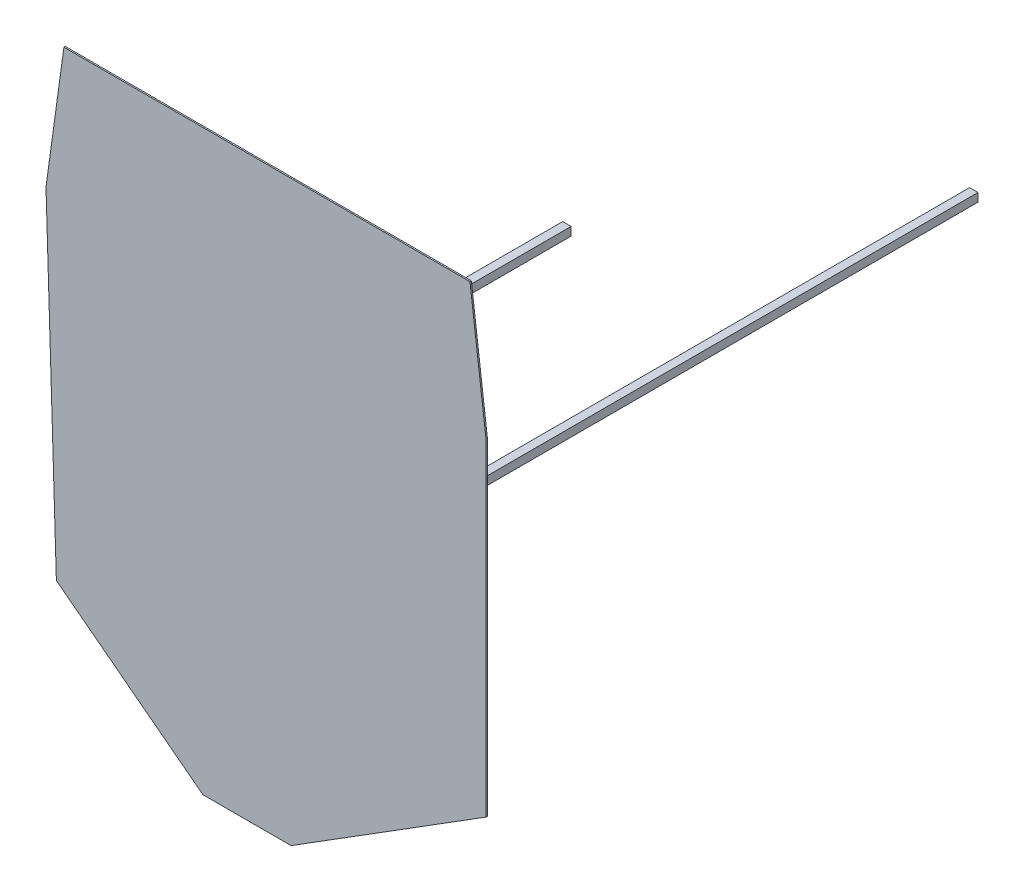
SolidWorks part; units mm, degrees
ref_plane "Front" through (0, 0, 0) normal (0, 0, 1) x (1, 0, 0)
ref_plane "Top" through (0, 0, 0) normal (0, 1, 0) x (1, 0, 0)
ref_plane "Right" through (0, 0, 0) normal (1, 0, 0) x (0, 0, -1)
sketch "Esquisse1" plane through (0, 0, 0) normal (0, 0, 1) x (1, 0, 0)
  line L1 (0, 0) -> (50, 0)
  line L2 (0, 0) -> (0, 50)
  line L3 (0, 50) -> (50, 50)
  line L4 (50, 0) -> (50, 50)
  dimension "D1" = 50
  dimension "D2" = 50
extrude "Boss.-Extru.1" add sketch "Esquisse1" along normal blind 5
sketch "Esquisse2" plane through (0, 0, 5) normal (0, 0, 1) x (1, 0, 0)
  line L0 (-5.6535, 9.3332) -> (57.2852, 53.4636)
  line L1 (57.2852, 53.4636) -> (231.6916, 53.4636)
  line L2 (231.6916, 53.4636) -> (285.9358, -3.0527)
  line L3 (285.9358, -3.0527) -> (284, -82.5096)
  line L4 (284, -82.5096) -> (207.7062, -129.7611)
  line L5 (207.7062, -129.7611) -> (50.4315, -129.7611)
  line L6 (50.4315, -129.7611) -> (-5.6535, -85.3866)
  line L7 (-5.6535, -85.3866) -> (-5.6535, 9.3332)
  line L8 (261, -129.7611) -> (23, -129.7611) construction
  line L9 (284, 24.7389) -> (284, -104.2611) construction
extrude "Boss.-Extru.2" add sketch "Esquisse2" against normal up to vertex (5 mm away) up to point (0, 50, 0)
sketch "Esquisse3" plane through (0, 0, 0) normal (0, 0, -1) x (-1, 0, 0)
  line L0 (0, -121.7217) -> (6, -121.7217)
  line L1 (6, -121.7217) -> (6, -115.7217)
  line L2 (6, -115.7217) -> (0, -115.7217)
  line L4 (0, -115.7217) -> (0, -121.7217)
  line L6 (-284, 44.2389) -> (-290, 44.2389)
  line L7 (-284, 44.2389) -> (-284, 50.2389)
  line L8 (-284, 50.2389) -> (-290, 50.2389)
  line L9 (-290, 44.2389) -> (-290, 50.2389)
  dimension "D1" = 6
  dimension "D2" = 6
  dimension "D3" = 6
  dimension "D4" = 6
extrude "Boss.-Extru.3" add sketch "Esquisse3" along normal blind 350
sketch "Esquisse4" plane through (0, 0, 5) normal (0, 0, 1) x (1, 0, 0)
  line L0 (-5.5339, 170.1435) -> (283.89, 170.1435)
  line L1 (283.89, 170.1435) -> (295.4804, 77.4204)
  line L2 (295.4804, 77.4204) -> (295.4804, -154.5668)
  line L3 (295.4804, -154.5668) -> (156.3957, -241.7353)
  line L4 (156.3957, -241.7353) -> (93.5299, -241.7353)
  line L5 (93.5299, -241.7353) -> (-10.9091, -161.7784)
  line L6 (-10.9091, -161.7784) -> (-18.3001, 77.4204)
  line L7 (-18.3001, 77.4204) -> (-5.5339, 170.1435)
extrude "Boss.-Extru.4" add sketch "Esquisse4" along normal blind 1
